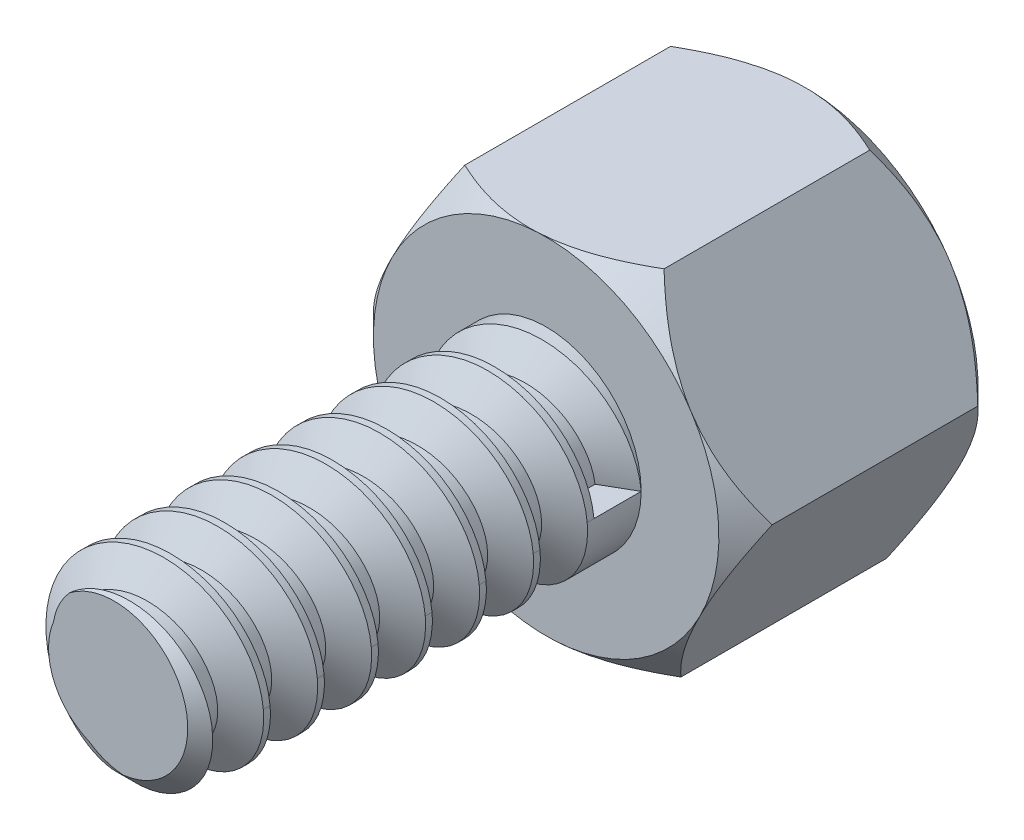
SolidWorks part; units mm, degrees
ref_plane "Front Plane" through (0, 0, 0) normal (0, 0, 1) x (1, 0, 0)
ref_plane "Top Plane" through (0, 0, 0) normal (0, 1, 0) x (1, 0, 0)
ref_plane "Right Plane" through (0, 0, 0) normal (1, 0, 0) x (0, 0, -1)
sketch "Sketch1" plane through (0, 0, 0) normal (0, 0, 1) x (1, 0, 0)
  line L1 (-2.1109, -4.1082) -> (2.5024, -3.8822)
  line L2 (2.5024, -3.8822) -> (4.6133, 0.2261)
  line L3 (4.6133, 0.2261) -> (2.1109, 4.1082)
  line L4 (2.1109, 4.1082) -> (-2.5024, 3.8822)
  line L5 (-2.5024, 3.8822) -> (-4.6133, -0.2261)
  line L6 (-4.6133, -0.2261) -> (-2.1109, -4.1082)
  circle A0 centre (0, 0) radius 4 construction
  dimension "D1" = 8
extrude "Boss-Extrude4" add sketch "Sketch1" along normal mid plane 6
sketch "Sketch14" plane through (0, 0, 3) normal (0, 0, 1) x (1, 0, 0)
  circle A0 centre (0, 0) radius 2.2
extrude "Boss-Extrude5" add sketch "Sketch14" along normal blind 10 contours A0
ref_plane "Plane5" through (2.1109, 4.1082, 3) normal (-0.5418, 0.8405, 0) x (0.8405, 0.5418, 0)
sketch "Sketch17" plane through (0, 0, -3) normal (0, 0, -1) x (-1, 0, 0)
  circle A0 centre (0, 0) radius 4
extrude "Cut-Extrude3" cut sketch "Sketch17" against normal blind 10 draft 45 flip side to cut
mirror "Mirror2" about plane through (0, 0, 0) normal (0, 0, 1) of "Cut-Extrude3"
chamfer "Chamfer2" distance 0.5 angle 45 1 edges at (2.2, 0, 13)
thread "Thread2" pitch 1.25 method cut profile "Thread Profile3" start angle 0, offset 0.0001, length 0, pitch 1.25, diameter 4.4
ref_plane "Plane7" through (2.2, 0, 3.0001) normal (0, -1, 0) x (1, 0, 0)
sketch "Thread Profile3" plane through (2.2, 0, 3.0001) normal (0, -1, 0) x (1, 0, 0)
  line L0 (0, 0) -> (0, 1.25) construction
  line L11 (0, 0) -> (0, 1.0937)
  line L12 (0, 1.0937) -> (-0.6766, 0.7031)
  line L13 (-0.6766, 0.7031) -> (-0.6766, 0.3906)
  line L15 (-0.6766, 0.3906) -> (0, 0)
  line L17 (-0.6766, 0.5469) -> (0, 0.5469) construction
  point P2 (0, 0)
  dimension "Pitch" = 1.25
  dimension "Profile_Angle" = 60
  dimension "Profile_Land" = 0.3125
  dimension "Profile_Height" = 0.6766
